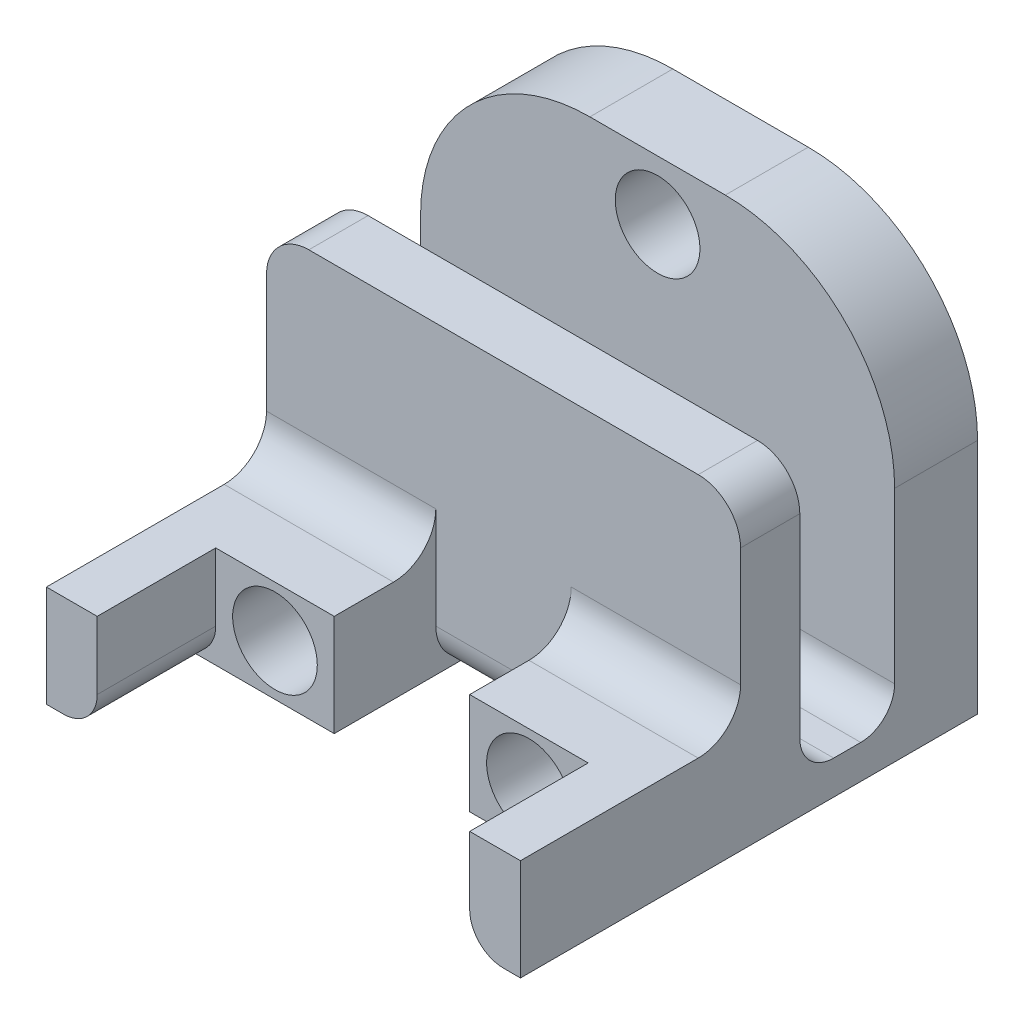
SolidWorks part; units mm, degrees
ref_plane "Front" through (0, 0, 0) normal (0, 0, 1) x (1, 0, 0)
ref_plane "Top" through (0, 0, 0) normal (0, 1, 0) x (1, 0, 0)
ref_plane "Right" through (0, 0, 0) normal (1, 0, 0) x (0, 0, -1)
sketch "Sketch1" plane through (0, 0, 0) normal (0, 1, 0) x (1, 0, 0)
  line L0 (0, 0) -> (0, 25.4)
  line L1 (0, 25.4) -> (35.56, 25.4)
  line L2 (35.56, 25.4) -> (35.56, 0)
  line L3 (31.75, 0) -> (22.86, 0)
  line L4 (22.86, 0) -> (22.86, 7.62)
  line L6 (12.7, 7.62) -> (12.7, 0)
  line L7 (12.7, 0) -> (3.81, 0)
  line L8 (3.81, 0) -> (3.81, -8.89)
  line L9 (3.81, -8.89) -> (0, -8.89)
  line L10 (0, -8.89) -> (0, 0)
  line L11 (0, 0) -> (0, -8.89)
  line L12 (31.75, 0) -> (31.75, -8.89)
  line L13 (31.75, -8.89) -> (35.56, -8.89)
  line L14 (35.56, -8.89) -> (35.56, 0)
  line L15 (12.7, 7.62) -> (22.86, 7.62)
  dimension "D1" = 8.89
  dimension "D2" = 7.62
  dimension "D3" = 25.4
  dimension "D4" = 10.16
  dimension "D5" = 35.56
extrude "Boss-Extrude1" add sketch "Sketch1" along normal blind 7.62 contours L6 L15 L4 L3 L12 L13 L14 L2 L1 L0 L10 L9 L8 L7 region at (17.78, 0, -12.1705)
sketch "Sketch2" plane through (0, 7.62, 0) normal (0, 1, 0) x (1, 0, 0)
  line L0 (0, 7.62) -> (35.56, 7.62)
  line L2 (35.56, -8.89) -> (35.56, 25.4) construction
  line L3 (0, -8.89) -> (0, 25.4) construction
  line L4 (0, 25.4) -> (35.56, 25.4) construction
  line L5 (0, 7.62) -> (0, 25.4)
  line L6 (35.56, 7.62) -> (35.56, 25.4)
  line L7 (0, 25.4) -> (35.56, 25.4)
  line L8 (12.7, 7.62) -> (22.86, 7.62) construction
  point P3 (17.78, 7.62)
extrude "Boss-Extrude2" add sketch "Sketch2" along normal blind 22.86
sketch "Sketch4" plane through (0, 30.48, 0) normal (0, 1, 0) x (1, 0, 0)
  line L0 (0, 19.177) -> (35.56, 19.177)
  line L1 (0, 25.4) -> (0, 7.62) construction
  line L2 (35.56, 7.62) -> (35.56, 25.4) construction
  line L3 (0, 12.065) -> (35.56, 12.065)
  line L4 (0, 19.177) -> (0, 12.065)
  line L5 (35.56, 19.177) -> (35.56, 12.065)
  line L6 (0, 7.62) -> (35.56, 7.62) construction
  dimension "D1" = 7.112
  dimension "D2" = 4.445
extrude "Cut-Extrude2" cut sketch "Sketch4" against normal blind 27.94
sketch "Sketch5" plane through (0, 30.48, 0) normal (0, 1, 0) x (1, 0, 0)
  line L0 (35.56, 7.62) -> (35.56, 12.065) construction
  line L1 (0, 7.62) -> (35.56, 7.62) construction
  line L2 (0, 12.065) -> (0, 7.62) construction
  line L3 (0, 12.065) -> (35.56, 12.065) construction
  line L4 (35.56, 7.62) -> (35.56, 12.065)
  line L5 (0, 7.62) -> (35.56, 7.62)
  line L6 (0, 12.065) -> (0, 7.62)
  line L7 (0, 12.065) -> (35.56, 12.065)
extrude "Cut-Extrude3" cut sketch "Sketch5" against normal blind 7.62
sketch "Sketch6" plane through (0, 0, -25.4) normal (0, 0, -1) x (-1, 0, 0)
  line L0 (-17.78, 30.48) -> (-17.78, 20.6523) construction
  line L1 (-35.56, 30.48) -> (0, 30.48) construction
  circle A0 centre (-17.78, 26.035) radius 3.175
  dimension "D1" = 6.35
  dimension "D2" = 4.445
extrude "Cut-Extrude4" cut sketch "Sketch6" against normal blind 6.35
sketch "Sketch7" plane through (0, 0, 0) normal (0, 0, 1) x (1, 0, 0)
  line L0 (27.305, 7.62) -> (27.305, 3.81) construction
  line L1 (31.75, 7.62) -> (22.86, 7.62) construction
  line L2 (27.305, 3.81) -> (22.86, 3.81) construction
  line L3 (22.86, 7.62) -> (22.86, 0) construction
  line L4 (17.78, 0) -> (17.78, 9.9153) construction
  line L5 (12.7, 0) -> (22.86, 0) construction
  line L6 (8.255, 3.81) -> (12.7, 3.81) construction
  line L7 (8.255, 7.62) -> (8.255, 3.81) construction
  circle A0 centre (27.305, 3.81) radius 3.175
  circle A1 centre (8.255, 3.81) radius 3.175
  dimension "D1" = 6.35
extrude "Cut-Extrude5" cut sketch "Sketch7" against normal blind 9.525
fillet "Fillet1" radius 12.7 2 edges at (0, 30.48, -22.2885) (35.56, 30.48, -22.2885)
fillet "Fillet2" radius 3.175 2 edges at (0, 22.86, -9.8425) (35.56, 22.86, -9.8425)
sketch "Sketch8" [suppressed] plane through (0, 7.62, 0) normal (0, 1, 0) x (1, 0, 0)
  line L0 (12.7, 7.62) -> (22.86, 7.62)
  line L1 (22.86, 7.62) -> (22.86, 0)
  line L2 (22.86, 0) -> (31.75, 0)
  line L3 (31.75, 0) -> (31.75, -8.89)
  line L4 (31.75, -8.89) -> (3.81, -8.89)
  line L5 (3.81, -8.89) -> (3.81, 0)
  line L6 (3.81, 0) -> (12.7, 0)
  line L7 (12.7, 0) -> (12.7, 7.62)
extrude "Boss-Extrude3" [suppressed] add sketch "Sketch8" against normal up to surface (7.62 mm away) up to face at (17.78, 0, -2.54)
sketch "Sketch9" [suppressed] plane through (0, 0, 0) normal (0, -1, 0) x (1, 0, 0)
  line L0 (0, 2.54) -> (35.56, 2.54)
  line L1 (0, 8.89) -> (0, -25.4) construction
  line L2 (35.56, 8.89) -> (35.56, -25.4) construction
  line L3 (35.56, 8.89) -> (0, 8.89) construction
  line L4 (0, 8.89) -> (0, 2.54)
  line L5 (35.56, 8.89) -> (35.56, 2.54)
  line L6 (35.56, 8.89) -> (0, 8.89)
  dimension "D1" = 6.35
extrude "Boss-Extrude4" [suppressed] add sketch "Sketch9" along normal blind 25.4
sketch "Sketch10" [suppressed] plane through (0, 0, 8.89) normal (0, 0, 1) x (1, 0, 0)
  line L0 (0, 0) -> (35.56, 0) construction
  line L1 (35.56, 7.62) -> (35.56, -25.4) construction
  line L2 (17.78, 0) -> (17.78, -25.4) construction
  line L3 (35.56, -25.4) -> (0, -25.4) construction
  line L4 (5.08, -12.7) -> (30.48, -12.7) construction
  circle A0 centre (5.08, -12.7) radius 2.5781
  circle A1 centre (17.78, -12.7) radius 1.5827
  circle A2 centre (30.48, -12.7) radius 1.2748
  point P12 (17.78, -12.7)
  point P13 (17.78, -12.7)
  dimension "D2" = 5.1562
  dimension "D1" = 25.4
sketch "Sketch11" [suppressed] plane through (0, 7.62, 0) normal (0, 1, 0) x (1, 0, 0)
  line L0 (0, -2.54) -> (35.56, -2.54)
  line L1 (0, -8.89) -> (0, 7.62) construction
  line L2 (35.56, -8.89) -> (35.56, 7.62) construction
  line L3 (0, -8.89) -> (35.56, -8.89) construction
  line L4 (35.56, -8.89) -> (35.56, -2.54)
  line L5 (0, -8.89) -> (35.56, -8.89)
  line L6 (0, -8.89) -> (0, -2.54)
  dimension "D1" = 6.35
extrude "Cut-Extrude6" [suppressed] cut sketch "Sketch11" against normal through all
sketch "Sketch12" [suppressed] plane through (0, 0, 2.54) normal (0, 0, 1) x (1, 0, 0)
  line L0 (17.78, 7.62) -> (17.78, 0) construction
  line L1 (35.56, 7.62) -> (0, 7.62) construction
  line L2 (35.56, 0) -> (0, 0) construction
  line L3 (17.78, 3.81) -> (0, 3.81) construction
  line L4 (0, 0) -> (0, 7.62) construction
  line L5 (17.78, 3.81) -> (35.56, 3.81) construction
  line L6 (35.56, 0) -> (35.56, 7.62) construction
  circle A0 centre (8.89, 3.81) radius 3.175
  circle A1 centre (26.67, 3.81) radius 3.175
  dimension "D1" = 6.35
extrude "Cut-Extrude7" [suppressed] cut sketch "Sketch12" against normal blind 7.62
fillet "Fillet3" radius 3.175 1 edges at (17.78, 0, -7.62)
fillet "Fillet4" [suppressed] radius 3.175
fillet "Fillet5" radius 3.175 2 edges at (29.21, 7.62, -7.62) (6.35, 7.62, -7.62)
fillet "Fillet6" radius 2.54 4 edges at (3.81, 0, 4.445) (31.75, 0, 4.445) (17.78, 2.54, -12.065) (17.78, 2.54, -19.177)
